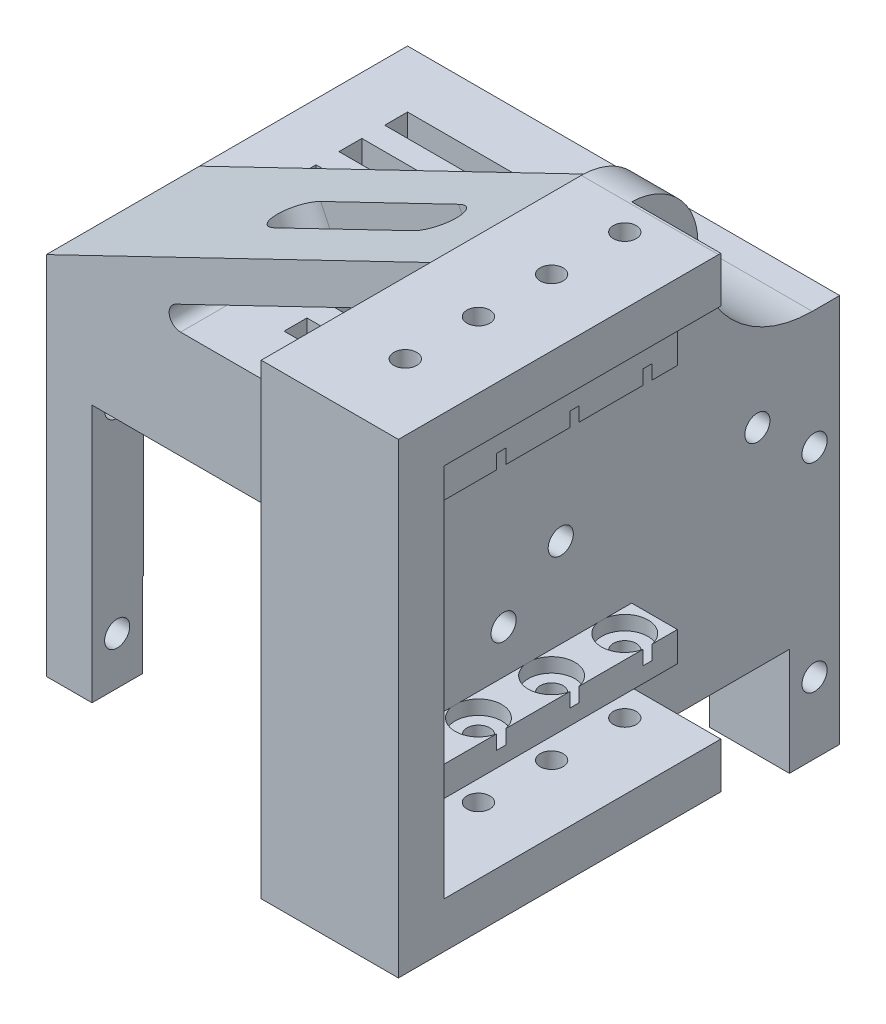
SolidWorks part; units mm, degrees
ref_plane "Front Plane" through (0, 0, 0) normal (0, 0, 1) x (1, 0, 0)
ref_plane "Top Plane" through (0, 0, 0) normal (0, 1, 0) x (1, 0, 0)
ref_plane "Right Plane" through (0, 0, 0) normal (1, 0, 0) x (0, 0, -1)
sketch "Sketch1" plane through (0, 0, 0) normal (0, 0, 1) x (1, 0, 0)
  line L1 (0, 0) -> (57.912, 0)
  line L2 (0, 0) -> (0, 63.754)
  line L3 (0, 63.754) -> (57.912, 63.754)
  line L4 (57.912, 0) -> (57.912, 63.754)
  dimension "D1" = 57.912
  dimension "D2" = 63.754
extrude "Boss-Extrude1" add sketch "Sketch1" against normal blind 58.928
sketch "Sketch3" plane through (0, 0, 0) normal (0, 0, 1) x (1, 0, 0)
  line L0 (42.672, 63.754) -> (0, 43.18)
  line L1 (42.672, 59.2423) -> (14.3644, 45.594)
  line L2 (14.9159, 43.18) -> (42.672, 43.18)
  line L3 (44.437, 60.0933) -> (1.765, 39.5193) construction
  line L4 (0, 63.754) -> (0, 0)
  line L5 (0, 0) -> (57.912, 0)
  line L6 (57.912, 0) -> (57.912, 63.754)
  line L7 (57.912, 63.754) -> (0, 63.754)
  line L8 (0, 63.754) -> (0, 43.18)
  line L9 (5.08, 0) -> (5.08, 31.242)
  line L10 (0, 0) -> (57.912, 0) construction
  line L11 (42.672, 63.754) -> (0, 63.754)
  line L12 (42.672, 59.2423) -> (42.672, 43.18)
  line L13 (5.08, 31.242) -> (39.116, 31.242)
  line L14 (39.116, 31.242) -> (39.116, 0)
  line L15 (5.08, 0) -> (39.116, 0)
  line L16 (48.006, 0) -> (48.006, 11.938)
  line L17 (48.006, 11.938) -> (57.912, 11.938)
  line L18 (57.912, 0) -> (57.912, 63.754) construction
  line L19 (57.912, 11.938) -> (57.912, 0)
  line L20 (48.006, 0) -> (57.912, 0)
  arc A0 (14.3644, 45.594) -> (14.9159, 43.18) centre (14.9159, 44.45) ccw
  dimension "D5" = 1.27
  dimension "D2" = 15.24
  dimension "D3" = 20.574
  dimension "D7" = 5.08
  dimension "D8" = 31.242
  dimension "D9" = 34.036
  dimension "D10" = 9.906
  dimension "D11" = 11.938
  dimension "D1" = 0
  dimension "D4" = 4.064
extrude "Cut-Extrude1" cut sketch "Sketch3" against normal through all
sketch "Sketch4" plane through (0, 63.754, 0) normal (0, 1, 0) x (1, 0, 0)
  line L0 (0, 0) -> (0, 18.796)
  line L1 (0, 58.928) -> (0, 0) construction
  line L2 (0, 18.796) -> (42.672, 18.796)
  line L3 (42.672, 58.928) -> (42.672, 0) construction
  line L4 (42.672, 18.796) -> (42.672, 0)
  line L5 (42.672, 0) -> (0, 0)
  line L6 (57.912, 35.814) -> (48.006, 35.814)
  line L7 (57.912, 58.928) -> (57.912, 0) construction
  line L8 (48.006, 35.814) -> (48.006, 58.928)
  line L9 (48.006, 58.928) -> (57.912, 58.928)
  line L10 (57.912, 58.928) -> (57.912, 35.814)
  line L11 (50.546, 35.814) -> (50.546, 32.512) construction
  circle A0 centre (50.546, 32.512) radius 1.27
  circle A1 centre (50.546, 24.384) radius 1.27
  circle A2 centre (50.546, 16.256) radius 1.27
  circle A3 centre (50.546, 8.128) radius 1.27
  dimension "D5" = 2.54
  dimension "D1" = 18.796
  dimension "D2" = 9.906
  dimension "D3" = 7.366
  dimension "D4" = 3.302
  dimension "D8" = 35.814
  dimension "D6" = 4
extrude "Cut-Extrude2" cut sketch "Sketch4" against normal through all
fillet "Fillet1" radius 2.54 1 edges at (42.672, 21.59, -18.796)
sketch "Sketch6" plane through (0, 63.754, 0) normal (0, 1, 0) x (1, 0, 0)
  line L0 (42.672, 35.814) -> (0, 35.814)
  line L1 (0, 58.928) -> (0, 18.796) construction
  line L2 (0, 35.814) -> (0, 58.928)
  line L3 (0, 58.928) -> (48.006, 58.928)
  line L4 (48.006, 58.928) -> (48.006, 43.18)
  line L5 (48.006, 58.928) -> (48.006, 35.814) construction
  line L6 (48.006, 43.18) -> (42.672, 43.18)
  line L7 (42.672, 58.928) -> (42.672, 18.796) construction
  line L8 (42.672, 43.18) -> (42.672, 35.814)
  line L9 (48.006, 35.814) -> (57.912, 35.814) construction
  dimension "D1" = 15.748
extrude "Cut-Extrude3" cut sketch "Sketch6" against normal blind 20.574
fillet "Fillet2" radius 12.7 1 edges at (45.339, 43.18, -43.18)
fillet "Fillet3" radius 7.62 1 edges at (42.672, 43.18, -36.068)
fillet "Fillet4" radius 7.62 1 edges at (45.339, 63.754, -43.18)
sketch "Sketch7" plane through (-16.8922, 35.0356, 0) normal (-0.4343, 0.9008, 0) x (0.9008, 0.4343, 0)
  line L0 (57.4899, 18.796) -> (57.4899, 24.638) construction
  line L1 (18.753, 18.796) -> (66.1259, 18.796) construction
  line L2 (57.4899, 24.638) -> (66.1259, 24.638) construction
  line L4 (57.4899, 24.638) -> (40.4719, 24.638)
  line L5 (57.4899, 29.718) -> (40.4719, 29.718)
  line L6 (66.1259, 35.56) -> (66.1259, 18.796) construction
  arc A0 (40.4719, 29.718) -> (40.4719, 24.638) centre (40.4719, 27.178) ccw
  arc A1 (57.4899, 29.718) -> (57.4899, 24.638) centre (57.4899, 27.178) cw
  dimension "D1" = 8.636
  dimension "D2" = 5.842
  dimension "D4" = 17.018
  dimension "D3" = 5.08
extrude "Cut-Extrude4" cut sketch "Sketch7" along direction (-0.4343, 0.9008, 0) on the side against the normal up to next (4.064 mm away)
sketch "Sketch8" plane through (0, 43.18, 0) normal (0, 1, 0) x (1, 0, 0)
  line L0 (6.35, 52.578) -> (34.29, 52.578)
  line L1 (34.29, 52.578) -> (34.29, 50.038)
  line L2 (34.29, 50.038) -> (6.35, 50.038)
  line L3 (6.35, 50.038) -> (6.35, 52.578)
  line L4 (0, 58.928) -> (0, 35.814) construction
  line L5 (0, 58.928) -> (48.006, 58.928) construction
  line L6 (34.29, 44.958) -> (6.35, 44.958)
  line L7 (34.29, 47.498) -> (34.29, 44.958)
  line L8 (6.35, 47.498) -> (34.29, 47.498)
  line L9 (6.35, 44.958) -> (6.35, 47.498)
  line L10 (34.29, 39.878) -> (6.35, 39.878)
  line L11 (34.29, 42.418) -> (34.29, 39.878)
  line L12 (6.35, 42.418) -> (34.29, 42.418)
  line L13 (6.35, 39.878) -> (6.35, 42.418)
  line L14 (34.29, 37.338) -> (20.574, 37.338)
  line L15 (34.29, 37.338) -> (34.29, 34.798)
  line L16 (34.29, 34.798) -> (20.574, 34.798)
  line L17 (20.574, 34.798) -> (20.574, 37.338)
  line L18 (34.29, 37.338) -> (6.35, 37.338) construction
  line L19 (34.29, 29.718) -> (20.574, 29.718)
  line L20 (34.29, 32.258) -> (34.29, 29.718)
  line L21 (34.29, 32.258) -> (20.574, 32.258)
  line L22 (20.574, 29.718) -> (20.574, 32.258)
  line L23 (34.29, 24.638) -> (20.574, 24.638)
  line L24 (34.29, 27.178) -> (34.29, 24.638)
  line L25 (34.29, 27.178) -> (20.574, 27.178)
  line L26 (20.574, 24.638) -> (20.574, 27.178)
  dimension "D1" = 6.35
  dimension "D2" = 6.35
  dimension "D3" = 2.54
  dimension "D4" = 27.94
  dimension "D7" = 2.54
  dimension "D8" = 13.716
  dimension "D6" = 2.54
  dimension "D5" = 3
  dimension "D9" = 3
extrude "Cut-Extrude5" cut sketch "Sketch8" against normal through all
sketch "Sketch9" plane through (0, 31.242, 0) normal (0, -1, 0) x (1, 0, 0)
  line L4 (39.116, -19.304) -> (5.08, -19.304)
  line L5 (5.08, -58.42) -> (39.116, -58.42)
  line L8 (39.116, -58.928) -> (39.116, -18.796)
  line L9 (39.116, -18.796) -> (5.08, -18.796)
  line L10 (5.08, -18.796) -> (5.08, -58.928)
  line L11 (5.08, -58.928) -> (39.116, -58.928)
  line L12 (39.116, -58.42) -> (39.116, -19.304)
  line L14 (5.08, -19.304) -> (5.08, -58.42)
  dimension "D1" = 0
extrude "Cut-Extrude6" cut sketch "Sketch9" against normal blind 5.588
sketch "Sketch10" plane through (5.08, 0, 0) normal (1, 0, 0) x (0, 0, -1)
  line L0 (58.42, 31.242) -> (54.6195, 36.83)
  line L1 (58.42, 36.83) -> (19.304, 36.83) construction
  line L2 (58.928, 31.242) -> (58.42, 31.242) construction
  line L3 (54.6195, 36.83) -> (58.42, 36.83)
  line L4 (58.42, 36.83) -> (58.42, 31.242)
  dimension "D1" = 124.22
extrude "Boss-Extrude3" add sketch "Sketch10" along direction (1, 0, 0) on the side of the normal up to next (34.036 mm away)
sketch "Sketch11" plane through (0, 31.242, 0) normal (0, -1, 0) x (1, 0, 0)
  line L0 (22.098, -58.928) -> (22.098, -18.796) construction
  line L1 (39.116, -58.928) -> (5.08, -58.928) construction
  line L2 (39.116, -18.796) -> (5.08, -18.796) construction
  line L3 (22.098, -38.862) -> (6.9192, -38.862) construction
ref_plane "Plane1" through (0, 0, -38.862) normal (0, 0, 1) x (1, 0, 0)
mirror "Mirror1" about plane through (0, 0, -38.862) normal (0, 0, 1) of "Boss-Extrude3"
fillet "Fillet5" radius 3.048 2 edges at (22.098, 36.83, -54.6195) (22.098, 36.83, -23.1045)
sketch "Sketch12" plane through (42.672, 0, 0) normal (-1, 0, 0) x (0, 0, 1)
  line L0 (0, 0) -> (0, 63.754) construction
  line L1 (-5.08, 27.94) -> (-12.954, 27.94)
  line L2 (-5.08, 27.94) -> (-5.08, 48.514)
  line L3 (-5.08, 48.514) -> (-12.954, 48.514)
  line L4 (-12.954, 27.94) -> (-12.954, 48.514)
  line L5 (0, 63.754) -> (-18.796, 63.754) construction
  line L6 (-53.34, 0) -> (-53.34, 11.938)
  line L7 (-58.928, 0) -> (-18.796, 0) construction
  line L8 (-53.34, 11.938) -> (-24.384, 11.938)
  line L9 (-24.384, 11.938) -> (-24.384, 2.5976)
  line L10 (-24.384, 2.5976) -> (-18.796, 2.5976)
  line L11 (-18.796, 0) -> (-18.796, 43.18) construction
  line L12 (-18.796, 2.5976) -> (-18.796, 11.938)
  line L13 (-18.796, 11.938) -> (0, 11.938)
  line L14 (0, 11.938) -> (0, 0)
  line L15 (0, 0) -> (-53.34, 0)
  line L16 (-58.928, 43.18) -> (-58.928, 0) construction
  dimension "D1" = 5.08
  dimension "D2" = 7.874
  dimension "D3" = 20.574
  dimension "D4" = 15.24
  dimension "D5" = 5.588
  dimension "D6" = 5.588
  dimension "D7" = 11.938
extrude "Cut-Extrude7" cut sketch "Sketch12" against normal through all both and the other way through all
sketch "Sketch14" plane through (0, 0, 0) normal (-1, 0, 0) x (0, 0, 1)
  line L0 (-53.34, 11.938) -> (-53.34, 32.258)
  line L1 (-53.34, 11.938) -> (-24.5287, 11.938)
  line L2 (-24.384, 11.938) -> (-53.34, 11.938) construction
  line L3 (-24.5287, 11.938) -> (-24.5287, 32.258)
  line L4 (-24.5287, 32.258) -> (-53.34, 32.258)
  dimension "D1" = 20.32
extrude "Cut-Extrude8" cut sketch "Sketch14" against normal up to surface (42.672 mm away) up to face at (42.672, 38.227, -9.017)
sketch "Sketch17" plane through (0, 0, 0) normal (-1, 0, 0) x (0, 0, 1)
  line L0 (-58.928, 0) -> (-53.34, 0) construction
  line L1 (-56.134, 0) -> (-56.134, 7.874) construction
  line L2 (-21.59, 2.5976) -> (-21.59, 0) construction
  line L3 (-18.796, 2.5976) -> (-24.384, 2.5976) construction
  line L4 (-38.862, 0) -> (-38.862, 39.1109) construction
  line L5 (-56.134, 0) -> (-21.59, 0) construction
  line L6 (-49.784, 32.258) -> (-49.784, 35.052) construction
  line L7 (-24.5287, 32.258) -> (-53.34, 32.258) construction
  circle A0 centre (-56.134, 7.874) radius 1.397
  circle A1 centre (-56.134, 29.972) radius 1.397
  circle A2 centre (-49.784, 35.052) radius 1.397
  circle A3 centre (-21.59, 7.874) radius 1.397
  circle A4 centre (-21.59, 29.972) radius 1.397
  circle A5 centre (-27.94, 35.052) radius 1.397
  dimension "D2" = 2.794
  dimension "D6" = 2.794
  dimension "D1" = 7.874
  dimension "D3" = 2
  dimension "D4" = 2.794
  dimension "D5" = 3.556
extrude "Cut-Extrude9" cut sketch "Sketch17" against normal through all
sketch "Sketch18" plane through (0, 0, -35.814) normal (0, 0, -1) x (-1, 0, 0)
  line L0 (-57.912, 58.6698) -> (-48.006, 58.6698)
  line L1 (-57.912, 11.938) -> (-57.912, 63.7498) construction
  line L2 (-48.006, 58.6698) -> (-48.006, 53.8438)
  line L3 (-48.006, 53.8438) -> (-53.086, 53.8438)
  line L4 (-53.086, 53.8438) -> (-53.086, 50.5418)
  line L5 (-53.086, 50.5418) -> (-48.006, 50.5418)
  line L6 (-48.006, 50.5418) -> (-48.006, 25.146)
  line L7 (-48.006, 37.8439) -> (-57.912, 37.8439) construction
  line L8 (-57.912, 17.018) -> (-57.912, 58.6698)
  line L9 (-57.912, 63.7519) -> (-57.912, 11.938) construction
  line L10 (-57.912, 63.754) -> (-57.912, 63.7498) construction
  line L11 (-48.006, 63.7498) -> (-57.912, 63.7498) construction
  line L12 (-57.912, 11.9359) -> (-57.912, 63.7498) construction
  line L13 (-53.086, 25.146) -> (-48.006, 25.146)
  line L14 (-53.086, 21.844) -> (-53.086, 25.146)
  line L15 (-48.006, 21.844) -> (-53.086, 21.844)
  line L16 (-48.006, 17.018) -> (-48.006, 21.844)
  line L17 (-57.912, 17.018) -> (-48.006, 17.018)
  point P15 (-57.912, 37.8449)
  dimension "D1" = 5.08
  dimension "D2" = 9.906
  dimension "D3" = 4.826
  dimension "D4" = 5.08
  dimension "D5" = 3.302
extrude "Cut-Extrude10" cut sketch "Sketch18" against normal blind 30.734
sketch "Sketch19" plane through (0, 25.146, 0) normal (0, 1, 0) x (1, 0, 0)
  circle A0 centre (50.546, 8.128) radius 1.27 construction
  circle A1 centre (50.546, 16.256) radius 1.27 construction
  circle A2 centre (50.546, 24.384) radius 1.27 construction
  circle A3 centre (50.546, 32.512) radius 1.27 construction
  circle A4 centre (50.546, 8.128) radius 1.27 construction
  circle A5 centre (50.546, 16.256) radius 1.27 construction
  circle A6 centre (50.546, 24.384) radius 1.27 construction
  circle A7 centre (50.546, 32.512) radius 1.27 construction
  circle A8 centre (50.546, 32.512) radius 2.5908
  circle A9 centre (50.546, 24.384) radius 2.5908
  circle A10 centre (50.546, 16.256) radius 2.5908
  circle A11 centre (50.546, 8.128) radius 2.5908
  dimension "D1" = 1.3208
  dimension "D2" = 1.3208
  dimension "D3" = 1.3208
  dimension "D4" = 1.3208
extrude "Cut-Extrude13" cut sketch "Sketch19" against normal blind 1.5875
sketch "Sketch20" plane through (0, 50.5418, 0) normal (0, -1, 0) x (1, 0, 0)
  circle A0 centre (50.546, -8.128) radius 1.27 construction
  circle A1 centre (50.546, -16.256) radius 1.27 construction
  circle A2 centre (50.546, -24.384) radius 1.27 construction
  circle A3 centre (50.546, -32.512) radius 1.27 construction
  circle A4 centre (50.546, -8.128) radius 1.27 construction
  circle A5 centre (50.546, -16.256) radius 1.27 construction
  circle A6 centre (50.546, -24.384) radius 1.27 construction
  circle A7 centre (50.546, -32.512) radius 1.27 construction
  circle A8 centre (50.546, -8.128) radius 2.5908
  circle A9 centre (50.546, -16.256) radius 2.5908
  circle A10 centre (50.546, -24.384) radius 2.5908
  circle A11 centre (50.546, -32.512) radius 2.5908
  dimension "D1" = 1.3208
  dimension "D2" = 1.3208
  dimension "D3" = 1.3208
  dimension "D4" = 1.3208
extrude "Cut-Extrude14" cut sketch "Sketch20" against normal blind 1.5875
